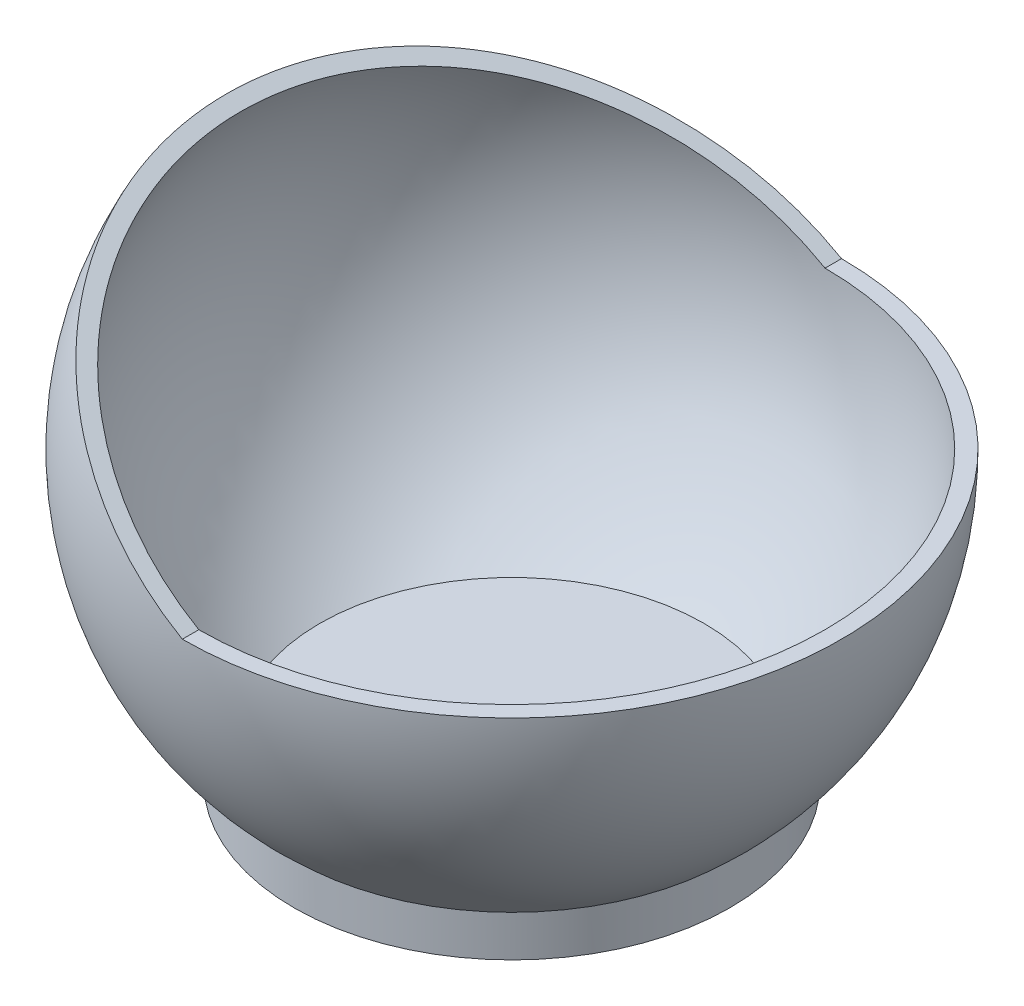
SolidWorks part; units mm, degrees
material "ABS"
ref_plane "Ön Düzlem" through (0, 0, 0) normal (0, 0, 1) x (1, 0, 0)
ref_plane "Üst Düzlem" through (0, 0, 0) normal (0, 1, 0) x (1, 0, 0)
ref_plane "Sağ Düzlem" through (0, 0, 0) normal (1, 0, 0) x (0, 0, -1)
sketch "Çizim1" plane through (0, 0, 0) normal (0, 0, 1) x (1, 0, 0)
  line L0 (0, 48.6422) -> (0, -48.6422) construction
  line L1 (0, 38) -> (0, 40)
  line L2 (0, -38) -> (0, -40)
  arc A0 (0, -40) -> (0, 40) centre (0, 0) ccw
  arc A1 (0, -38) -> (0, 38) centre (0, 0) ccw
  dimension "D1" = 80
  dimension "D2" = 76
revolve "Döndür1" add sketch "Çizim1" angle 360 about L0
sketch "Çizim2" plane through (0, 0, 0) normal (0, 0, 1) x (1, 0, 0)
  line L0 (0, 0) -> (40, 0)
  line L1 (0, 0) -> (-34.641, 20)
  line L3 (-26.4575, -30) -> (26.4575, -30)
  line L4 (-26.4575, -30) -> (-26.4575, -50)
  line L5 (-26.4575, -50) -> (26.4575, -50)
  line L6 (26.4575, -30) -> (26.4575, -50)
  line L7 (-26.4575, -30) -> (26.4575, -50) construction
  line L8 (-26.4575, -50) -> (26.4575, -30) construction
  circle A0 centre (0, 0) radius 40 construction
  arc A1 (40, 0) -> (-34.641, 20) centre (0, 0) ccw
  point P5 (0, -40)
  dimension "D1" = 150
  dimension "D2" = 30
extrude "Kes-Ekstrüzyon1" cut sketch "Çizim2" against normal through all both and the other way through all
sketch "Çizim4" plane through (0, -30, 0) normal (0, -1, 0) x (1, 0, 0)
  circle A0 centre (0, 0) radius 26.4575
  circle A1 centre (0, 0) radius 26.4575 construction
extrude "Yükseklik-Ekstrüzyon1" add sketch "Çizim4" along normal blind 5
sketch "Çizim13" plane through (0, 0, 0) normal (0, 0, 1) x (1, 0, 0)
  line L0 (-17.2047, -35) -> (-31.4575, -35)
  line L1 (-26.4575, -35) -> (26.4575, -35) construction
  line L2 (-31.4575, -35) -> (-31.4575, -23.0527)
  line L3 (-26.4575, -30) -> (-26.4575, -35) construction
  arc A0 (-31.4575, -23.0527) -> (-17.2047, -35) centre (0, 0) ccw
  dimension "D1" = 78
  dimension "D2" = 5
extrude "Yükseklik-Ekstrüzyon5" add sketch "Çizim13" along normal blind 5 and the other way blind 5
fillet "Radyus1" [suppressed] radius 0.5
